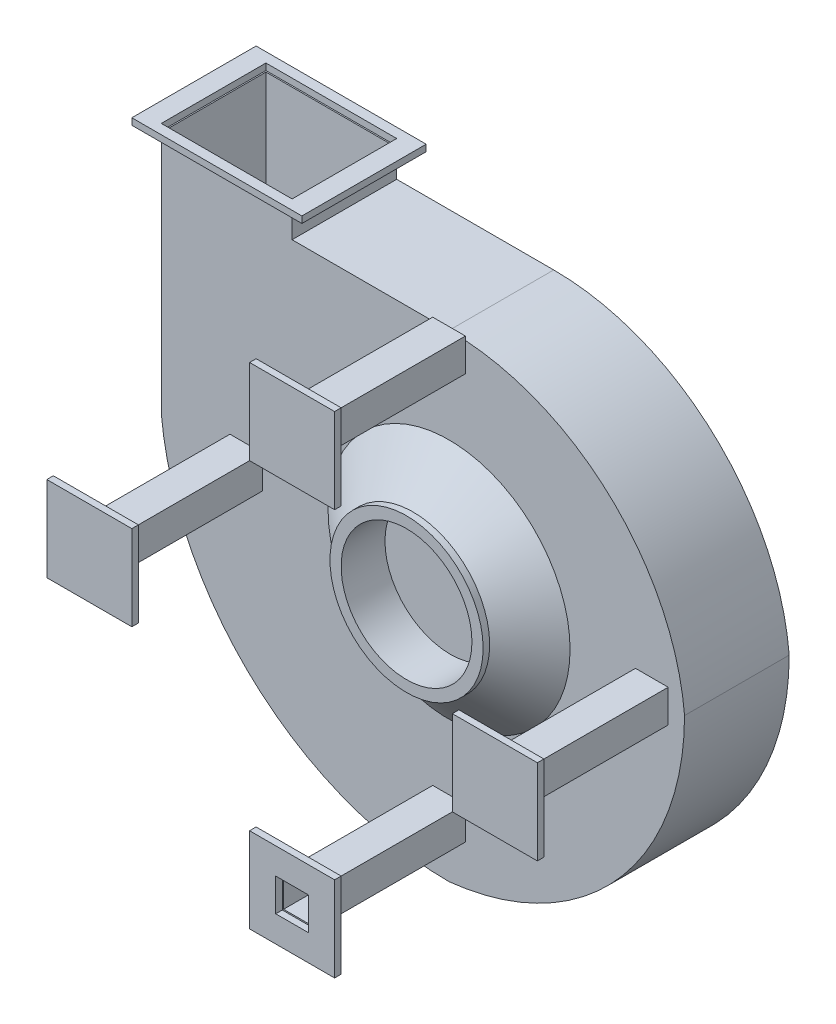
SolidWorks part; units mm, degrees
ref_plane "Front Plane" through (0, 0, 0) normal (0, 0, 1) x (1, 0, 0)
ref_plane "Top Plane" through (0, 0, 0) normal (0, 1, 0) x (1, 0, 0)
ref_plane "Right Plane" through (0, 0, 0) normal (1, 0, 0) x (0, 0, -1)
sketch "Sketch2" plane through (0, 0, 0) normal (0, 0, 1) x (1, 0, 0)
  line L0 (-178.5969, -100.0998) -> (621.4031, -100.0998) construction
  line L1 (261.4031, 229.9002) -> (261.4031, -500.0998) construction
  line L2 (-178.5969, -100.0998) -> (-178.5969, 273.9002)
  line L3 (-178.5969, 273.9002) -> (21.4031, 273.9002)
  line L4 (21.4031, 273.9002) -> (21.4031, 229.9002)
  line L5 (21.4031, 229.9002) -> (261.4031, 229.9002)
  arc A0 (261.4031, 229.9002) -> (621.4031, -100.0998) centre (261.4031, -131.4634) cw
  arc A1 (621.4031, -100.0998) -> (261.4031, -500.0998) centre (219.1809, -100.0998) cw
  arc A2 (261.4031, -500.0998) -> (-178.5969, -100.0998) centre (261.4031, -58.0998) cw
  dimension "D1" = 800
  dimension "D2" = 730
  dimension "D3" = 330
  dimension "D4" = 360
  dimension "D5" = 44
  dimension "D6" = 200
extrude "Boss-Extrude1" add sketch "Sketch2" along normal blind 160
shell "Shell1" thickness 2 removed face at (-78.5969, 273.9002, 80)
sketch "Sketch4" plane through (0, 0, 160) normal (0, 0, 1) x (1, 0, 0)
  line L0 (-178.5969, -100.0998) -> (621.4031, -100.0998) construction
  line L1 (261.4031, 229.9002) -> (261.4031, -500.0998) construction
  circle A0 centre (261.4031, -100.0998) radius 90
  dimension "D1" = 180
extrude "Cut-Extrude1" cut sketch "Sketch4" against normal blind 54
sketch "Sketch5" plane through (0, 0, 160) normal (0, 0, 1) x (1, 0, 0)
  line L0 (-178.5969, -100.0998) -> (621.4031, -100.0998) construction
  line L1 (261.4031, 229.9002) -> (261.4031, -500.0998) construction
  circle A0 centre (261.4031, -100.0998) radius 185
  dimension "D1" = 370
extrude "Boss-Extrude2" add sketch "Sketch5" along normal blind 55 draft 51
sketch "Sketch6" plane through (0, 0, 215) normal (0, 0, 1) x (1, 0, 0)
  circle A1 centre (261.4031, -100.0998) radius 117.0807
  circle A2 centre (261.4031, -100.0998) radius 117.0807
  dimension "D1" = 0
extrude "Boss-Extrude3" add sketch "Sketch6" along normal blind 10
sketch "Sketch7" plane through (0, 0, 225) normal (0, 0, 1) x (1, 0, 0)
  circle A0 centre (261.4031, -100.0998) radius 100
  dimension "D1" = 200
extrude "Cut-Extrude2" cut sketch "Sketch7" against normal blind 117
sketch "Sketch8" plane through (0, 0, 0) normal (0, 0, -1) x (-1, 0, 0)
  line L0 (178.5969, -100.0998) -> (-621.4031, -100.0998) construction
  circle A0 centre (-262.6233, -100.0998) radius 10
  dimension "D1" = 20
extrude "Cut-Extrude3" cut sketch "Sketch8" against normal blind 117
sketch "Sketch11" plane through (0, 273.9002, 0) normal (0, 1, 0) x (1, 0, 0)
  line L1 (-208.5969, 15) -> (51.4031, 15)
  line L2 (-208.5969, 15) -> (-208.5969, -175)
  line L3 (-208.5969, -175) -> (51.4031, -175)
  line L4 (21.4031, 0) -> (-178.5969, 0)
  line L5 (-178.5969, 0) -> (-178.5969, -160)
  line L6 (-178.5969, -160) -> (21.4031, -160)
  line L7 (21.4031, -160) -> (21.4031, 0)
  line L8 (21.4031, 0) -> (-178.5969, 0)
  line L9 (-178.5969, 0) -> (-178.5969, -160)
  line L10 (-178.5969, -160) -> (21.4031, -160)
  line L11 (21.4031, -160) -> (21.4031, 0)
  line L12 (51.4031, 15) -> (51.4031, -175)
  dimension "D2" = 30
  dimension "D3" = 30
  dimension "D4" = 15
  dimension "D5" = 15
  dimension "D1" = 0
extrude "Boss-Extrude5" add sketch "Sketch11" along normal blind 10 separate body
sketch "Sketch12" plane through (0, 0, 160) normal (0, 0, 1) x (1, 0, 0)
  line L0 (-178.5969, -100.0998) -> (621.4031, -100.0998) construction
  line L1 (-73.5969, -125.0998) -> (-23.5969, -125.0998)
  line L2 (-73.5969, -125.0998) -> (-73.5969, -75.0998)
  line L3 (-73.5969, -75.0998) -> (-23.5969, -75.0998)
  line L4 (-23.5969, -125.0998) -> (-23.5969, -75.0998)
  line L5 (-73.5969, -125.0998) -> (-23.5969, -75.0998) construction
  line L6 (-73.5969, -75.0998) -> (-23.5969, -125.0998) construction
  line L7 (261.4031, 229.9002) -> (261.4031, -500.0998) construction
  line L8 (286.4031, 234.9002) -> (286.4031, 184.9002)
  line L9 (236.4031, 234.9002) -> (286.4031, 234.9002)
  line L10 (236.4031, 234.9002) -> (236.4031, 184.9002)
  line L11 (236.4031, 184.9002) -> (286.4031, 184.9002)
  line L12 (596.4031, -125.0998) -> (546.4031, -125.0998)
  line L13 (596.4031, -75.0998) -> (596.4031, -125.0998)
  line L14 (596.4031, -75.0998) -> (546.4031, -75.0998)
  line L15 (546.4031, -75.0998) -> (546.4031, -125.0998)
  line L16 (236.4031, -435.0998) -> (236.4031, -385.0998)
  line L17 (286.4031, -435.0998) -> (236.4031, -435.0998)
  line L18 (286.4031, -435.0998) -> (286.4031, -385.0998)
  line L19 (286.4031, -385.0998) -> (236.4031, -385.0998)
  point P0 (-48.5969, -100.0998)
  point P24 (261.4031, -100.0998)
  dimension "D1" = 310
  dimension "D2" = 50
  dimension "D3" = 50
  dimension "D4" = 4
extrude "Extrude-Thin1" add sketch "Sketch12" along normal blind 230 thin thin type one direction reverse wall 2
sketch "Sketch16" plane through (0, 0, 390) normal (0, 0, 1) x (1, 0, 0)
  line L0 (16.4031, -35.0998) -> (16.4031, -165.0998)
  line L4 (286.4031, -385.0998) -> (236.4031, -385.0998)
  line L5 (236.4031, -385.0998) -> (236.4031, -435.0998)
  line L6 (236.4031, -435.0998) -> (286.4031, -435.0998)
  line L7 (286.4031, -435.0998) -> (286.4031, -385.0998)
  line L8 (286.4031, -385.0998) -> (236.4031, -385.0998)
  line L9 (236.4031, -385.0998) -> (236.4031, -435.0998)
  line L10 (236.4031, -435.0998) -> (286.4031, -435.0998)
  line L11 (286.4031, -435.0998) -> (286.4031, -385.0998)
  line L13 (196.4031, -345.0998) -> (326.4031, -345.0998)
  line L14 (196.4031, -345.0998) -> (196.4031, -475.0998)
  line L15 (196.4031, -475.0998) -> (326.4031, -475.0998)
  line L16 (326.4031, -345.0998) -> (326.4031, -475.0998)
  line L17 (16.4031, -165.0998) -> (-113.5969, -165.0998)
  line L18 (-113.5969, -35.0998) -> (-113.5969, -165.0998)
  line L19 (16.4031, -35.0998) -> (-113.5969, -35.0998)
  line L20 (326.4031, 144.9002) -> (196.4031, 144.9002)
  line L21 (196.4031, 144.9002) -> (196.4031, 274.9002)
  line L22 (326.4031, 274.9002) -> (196.4031, 274.9002)
  line L23 (326.4031, 144.9002) -> (326.4031, 274.9002)
  line L24 (506.4031, -165.0998) -> (506.4031, -35.0998)
  line L25 (506.4031, -35.0998) -> (636.4031, -35.0998)
  line L26 (636.4031, -165.0998) -> (636.4031, -35.0998)
  line L27 (506.4031, -165.0998) -> (636.4031, -165.0998)
  point P23 (261.4031, -100.0998)
  dimension "D2" = 40
  dimension "D3" = 40
  dimension "D4" = 40
  dimension "D5" = 40
  dimension "D1" = 0
  dimension "D6" = 4
extrude "Boss-Extrude6" add sketch "Sketch16" along normal blind 10 separate body
